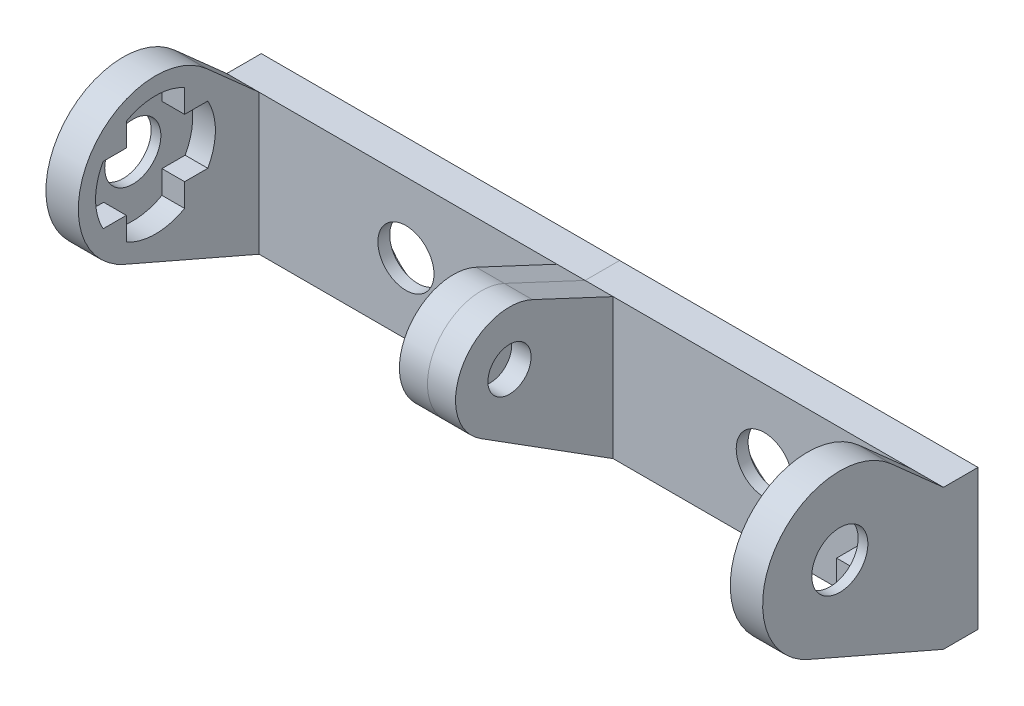
SolidWorks part; units mm, degrees
ref_plane "正面" through (0, 0, 0) normal (0, 0, 1) x (1, 0, 0)
ref_plane "平面" through (0, 0, 0) normal (0, 1, 0) x (1, 0, 0)
ref_plane "右側面" through (0, 0, 0) normal (1, 0, 0) x (0, 0, -1)
sketch "ｽｹｯﾁ1" plane through (0, 0, 0) normal (0, 0, 1) x (1, 0, 0)
  line L0 (0, 0) -> (13.6216, 0)
  line L1 (33.2, 0) -> (33.2, 13.0002)
  line L2 (33.2, 13.0002) -> (19.5784, 13.0002)
  line L3 (0, 13.0002) -> (0, 0)
  line L4 (16.6, 12.0053) -> (16.6, 0) construction
  line L5 (16.6, 6.5001) -> (33.2, 6.5001) construction
  line L6 (13.9218, 11.3099) -> (13.9218, 9.1783) construction
  line L7 (13.9218, 9.1783) -> (11.7902, 9.1783) construction
  line L8 (11.7902, 3.8219) -> (13.9218, 3.8219) construction
  line L9 (13.9218, 3.8219) -> (13.9218, 1.6903) construction
  line L10 (19.2782, 1.6903) -> (19.2782, 3.8219) construction
  line L11 (19.2782, 3.8219) -> (21.4098, 3.8219) construction
  line L12 (21.4098, 9.1783) -> (19.2782, 9.1783) construction
  line L13 (19.2782, 9.1783) -> (19.2782, 11.3099) construction
  line L14 (13.6216, 13.0002) -> (0, 13.0002)
  line L15 (19.5784, 0) -> (33.2, 0)
  line L16 (13.6216, 13.0002) -> (19.5784, 13.0002)
  line L17 (19.5784, 0) -> (13.6216, 0)
  line L18 (16.6, 12.0053) -> (16.6, 13.0002) construction
  arc A1 (11.7902, 9.1783) -> (11.7902, 3.8219) centre (16.6, 6.5001) ccw construction
  arc A2 (13.9218, 1.6903) -> (19.2782, 1.6903) centre (16.6, 6.5001) ccw construction
  arc A3 (21.4098, 3.8219) -> (21.4098, 9.1783) centre (16.6, 6.5001) ccw construction
  arc A4 (19.2782, 11.3099) -> (13.9218, 11.3099) centre (16.6, 6.5001) ccw construction
  dimension "D1" = 0.995
extrude "ﾎﾞｽ - 押し出し1" add sketch "ｽｹｯﾁ1" along normal blind 3.2
sketch "ｽｹｯﾁ2" plane through (0, 0, 0) normal (-1, 0, 0) x (0, 0, 1)
  line L3 (3.1997, 0) -> (15.472, 7.7447)
  line L4 (10.6849, 16.502) -> (3.1997, 13.0002)
  line L5 (3.1997, 13.0002) -> (3.1997, 0)
  arc A0 (15.472, 7.7447) -> (10.6849, 16.502) centre (12.8036, 11.9731) ccw
extrude "ﾎﾞｽ - 押し出し2" add sketch "ｽｹｯﾁ2" against normal blind 2.6
sketch "ｽｹｯﾁ3" plane through (33.2, 0, 0) normal (1, 0, 0) x (0, 0, -1)
  line L2 (-3.1997, 13.0002) -> (-8.0519, 17.3157)
  line L3 (-15.6549, 5.4162) -> (-3.1997, 0)
  line L5 (-3.1997, 13.0002) -> (-3.1997, 0)
  arc A0 (-8.0519, 17.3157) -> (-15.6549, 5.4162) centre (-12.8036, 11.9731) ccw
extrude "ﾎﾞｽ - 押し出し3" add sketch "ｽｹｯﾁ3" against normal blind 3
sketch "ｽｹｯﾁ4" plane through (0, 0, 0) normal (0, 0, -1) x (-1, 0, 0)
  line L0 (-21.833, 8.0233) -> (-20.3097, 6.5001)
  line L1 (-20.3097, 6.5001) -> (-21.833, 4.9769)
  line L2 (-18.1232, 1.2672) -> (-16.6, 2.7904)
  line L3 (-16.6, 2.7904) -> (-15.0768, 1.2672)
  line L4 (-11.367, 4.9769) -> (-12.8903, 6.5001)
  line L5 (-12.8903, 6.5001) -> (-11.367, 8.0233)
  line L6 (-21.8948, 8.0074) -> (-20.3875, 6.5001) construction
  line L7 (-20.3875, 6.5001) -> (-21.8948, 4.9929) construction
  line L8 (-18.1073, 1.2053) -> (-16.6, 2.7126) construction
  line L9 (-16.6, 2.7126) -> (-15.0927, 1.2053) construction
  line L10 (-11.3052, 4.9929) -> (-12.8125, 6.5001) construction
  line L11 (-12.8125, 6.5001) -> (-11.3052, 8.0074) construction
  line L12 (-15.0927, 11.7949) -> (-16.6, 10.2876) construction
  line L13 (-16.6, 10.2876) -> (-18.1073, 11.7949) construction
  line L14 (-15.0768, 11.7331) -> (-16.6, 10.2099)
  line L15 (-16.6, 10.2099) -> (-18.1232, 11.7331)
  arc A0 (-21.833, 4.9769) -> (-18.1232, 1.2672) centre (-16.6, 6.5001) ccw
  arc A1 (-21.8948, 4.9929) -> (-18.1073, 1.2053) centre (-16.6, 6.5001) ccw construction
  arc A2 (-15.0927, 1.2053) -> (-11.3052, 4.9929) centre (-16.6, 6.5001) ccw construction
  arc A3 (-11.3052, 8.0074) -> (-15.0927, 11.7949) centre (-16.6, 6.5001) ccw construction
  arc A4 (-18.1073, 11.7949) -> (-21.8948, 8.0074) centre (-16.6, 6.5001) ccw construction
  arc A5 (-15.0768, 1.2672) -> (-11.367, 4.9769) centre (-16.6, 6.5001) ccw
  arc A6 (-11.367, 8.0233) -> (-15.0768, 11.7331) centre (-16.6, 6.5001) ccw
  arc A7 (-18.1232, 11.7331) -> (-21.833, 8.0233) centre (-16.6, 6.5001) ccw
  dimension "D1" = 5.5051
extrude "ｶｯﾄ - 押し出し1" cut sketch "ｽｹｯﾁ4" against normal blind 2.1
sketch "ｽｹｯﾁ5" plane through (0, 0, 2.1) normal (0, 0, -1) x (-1, 0, 0)
  circle A0 centre (-16.6, 6.5001) radius 2.6
  dimension "D1" = 5.2
extrude "ｶｯﾄ - 押し出し2" cut sketch "ｽｹｯﾁ5" against normal up to vertex (1.1 mm away) up to point (30.2, 13.0002, 3.2)
sketch "ｽｹｯﾁ6" plane through (30.2, 0, 0) normal (-1, 0, 0) x (0, 0, 1)
  line L3 (15.5036, 7.1241) -> (15.5036, 9.2731)
  line L4 (15.5036, 9.2731) -> (17.6526, 9.2731)
  line L5 (17.6526, 14.6731) -> (15.5036, 14.6731)
  line L6 (15.5036, 14.6731) -> (15.5036, 16.8221)
  line L7 (10.1036, 16.8221) -> (10.1036, 14.6731)
  line L8 (10.1036, 14.6731) -> (7.9546, 14.6731)
  line L9 (7.9546, 9.2731) -> (10.1036, 9.2731)
  line L10 (10.1036, 9.2731) -> (10.1036, 7.1241)
  arc A1 (17.6526, 9.2731) -> (17.6526, 14.6731) centre (12.8036, 11.9731) ccw
  arc A2 (15.5036, 16.8221) -> (10.1036, 16.8221) centre (12.8036, 11.9731) ccw
  arc A3 (7.9546, 14.6731) -> (7.9546, 9.2731) centre (12.8036, 11.9731) ccw
  arc A4 (10.1036, 7.1241) -> (15.5036, 7.1241) centre (12.8036, 11.9731) ccw
extrude "ｶｯﾄ - 押し出し3" cut sketch "ｽｹｯﾁ6" against normal blind 2.1
sketch "ｽｹｯﾁ7" plane through (32.3, 0, 0) normal (-1, 0, 0) x (0, 0, 1)
  circle A0 centre (12.8036, 11.9731) radius 2.6
  dimension "D1" = 5.2
extrude "ｶｯﾄ - 押し出し4" cut sketch "ｽｹｯﾁ7" against normal up to vertex (0.9 mm away) up to point (33.2, 17.3157, 8.0519)
sketch "ｽｹｯﾁ8" plane through (2.6, 0, 0) normal (1, 0, 0) x (0, 0, -1)
  circle A0 centre (-12.8036, 11.9731) radius 2
  dimension "D1" = 4
extrude "ｶｯﾄ - 押し出し5" cut sketch "ｽｹｯﾁ8" against normal blind 1.8
mirror "ﾐﾗｰ1" about plane through (0, 0, 0) normal (1, 0, 0) of bodies 108
